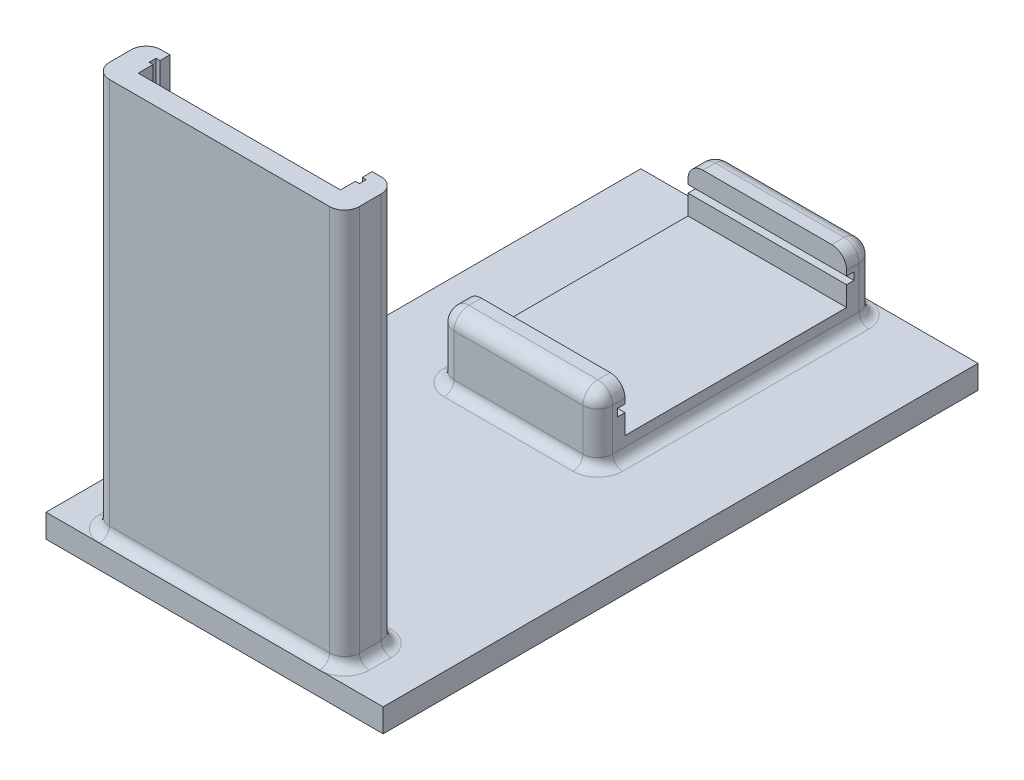
SolidWorks part; units mm, degrees
material "Melamine resin"
ref_plane "Front Plane" through (0, 0, 0) normal (0, 0, 1) x (1, 0, 0)
ref_plane "Top Plane" through (0, 0, 0) normal (0, 1, 0) x (1, 0, 0)
ref_plane "Right Plane" through (0, 0, 0) normal (1, 0, 0) x (0, 0, -1)
sketch "Sketch2" plane through (0, 0, 0) normal (0, 1, 0) x (1, 0, 0)
  line L1 (0, 0) -> (88.9, 0)
  line L2 (0, 0) -> (0, 152.4)
  line L3 (0, 152.4) -> (88.9, 152.4)
  line L10 (88.9, 152.4) -> (88.9, 0)
  dimension "D1" = 152.4
  dimension "D2" = 88.9
extrude "Boss-Extrude1" add sketch "Sketch2" along normal blind 5.9944 contours L3 L10 L1 L2
sketch "Sketch4" plane through (0, 5.9944, 0) normal (0, 1, 0) x (1, 0, 0)
  line L0 (0, 0) -> (0, 152.4) construction
  line L1 (0, 0) -> (88.9, 0) construction
  circle A0 centre (45.72, 109.8713) radius 2.7305
  circle A1 centre (45.72, 33.6713) radius 2.7305
  dimension "D3" = 5.461
  dimension "D4" = 5.461
  dimension "D1" = 76.2
  dimension "D2" = 45.72
  dimension "D5" = 33.6713
extrude "Cut-Extrude2" cut sketch "Sketch4" against normal through all both
sketch "Sketch5" plane through (0, 5.9944, 0) normal (0, 1, 0) x (1, 0, 0)
  line L0 (0, 152.4) -> (88.9, 152.4) construction
  line L1 (12.446, 15.748) -> (76.454, 15.748)
  line L2 (12.446, 15.748) -> (12.446, 2.54)
  line L3 (12.446, 2.54) -> (76.454, 2.54)
  line L4 (76.454, 15.748) -> (76.454, 2.54)
  line L5 (18.542, 7.62) -> (70.358, 7.62)
  line L6 (18.542, 7.62) -> (18.542, 15.748)
  line L7 (18.542, 15.748) -> (70.358, 15.748)
  line L8 (70.358, 7.62) -> (70.358, 15.748)
  line L9 (17.526, 13.208) -> (71.374, 13.208)
  line L10 (17.526, 13.208) -> (17.526, 11.43)
  line L11 (17.526, 11.43) -> (71.374, 11.43)
  line L12 (71.374, 13.208) -> (71.374, 11.43)
  line L13 (0, 0) -> (88.9, 0) construction
  point P16 (44.45, 152.4)
  point P17 (44.45, 15.748)
  dimension "D1" = 53.848
  dimension "D2" = 1.016
  dimension "D3" = 1.016
  dimension "D4" = 3.81
  dimension "D5" = 2.54
  dimension "D6" = 5.08
  dimension "D7" = 5.08
  dimension "D8" = 1.778
  dimension "D9" = 2.54
  dimension "D10" = 5.08
extrude "Boss-Extrude2" add sketch "Sketch5" along normal blind 101.6 contours L9 L12 L11 L8 L5 L6 L10 L1 L2 L3 L4 region at (44.45, 5.9944, -6.5736)
fillet "Fillet1" radius 3.81 4 edges at (12.446, 56.7944, -2.54) (12.446, 56.7944, -15.748) (76.454, 56.7944, -2.54) (76.454, 56.7944, -15.748)
fillet "Fillet2" radius 2.54 9 edges at (17.399, 5.9944, -15.748) (13.5619, 5.9944, -14.6321) (12.446, 5.9944, -9.144) (13.5619, 5.9944, -3.6559) (71.501, 5.9944, -15.748) (75.3381, 5.9944, -14.6321) (76.454, 5.9944, -9.144) (75.3381, 5.9944, -3.6559) (44.45, 5.9944, -2.54)
ref_plane "Plane1" through (44.45, 0, 0) normal (-1, 0, 0) x (0, 0, 1)
sketch "Sketch6" plane through (44.45, 0, 0) normal (-1, 0, 0) x (0, 0, 1)
  line L0 (0, 5.9944) -> (-152.4, 5.9944) construction
  line L1 (0, 5.9944) -> (-152.4, 5.9944)
  line L3 (-149.86, 5.9944) -> (-79.121, 5.9944)
  line L4 (-149.86, 5.9944) -> (-149.86, 23.1394)
  line L5 (-149.86, 23.1394) -> (-79.121, 23.1394)
  line L6 (-79.121, 5.9944) -> (-79.121, 23.1394)
  line L7 (-142.875, 23.1394) -> (-86.106, 23.1394)
  line L8 (-142.875, 23.1394) -> (-142.875, 11.0744)
  line L9 (-142.875, 11.0744) -> (-86.106, 11.0744)
  line L10 (-86.106, 23.1394) -> (-86.106, 11.0744)
  line L11 (-144.78, 18.0594) -> (-84.201, 18.0594)
  line L12 (-144.78, 18.0594) -> (-144.78, 16.1544)
  line L13 (-144.78, 16.1544) -> (-84.201, 16.1544)
  line L14 (-84.201, 18.0594) -> (-84.201, 16.1544)
  line L15 (-152.4, 5.9944) -> (-152.4, 0) construction
  dimension "D1" = 60.579
  dimension "D2" = 1.905
  dimension "D3" = 1.905
  dimension "D4" = 1.905
  dimension "D5" = 5.08
  dimension "D6" = 5.08
  dimension "D7" = 5.08
  dimension "D8" = 5.08
  dimension "D9" = 5.08
  dimension "D10" = 2.54
extrude "Boss-Extrude3" add sketch "Sketch6" along normal mid plane 40.64 contours L11 L14 L13 L10 L9 L8 L12 L5 L4 L1 L6 region at (44.45, 6.7223, -114.4905)
fillet "Fillet3" radius 3.81 2 edges at (44.45, 23.1394, -79.121) (44.45, 23.1394, -149.86)
fillet "Fillet6" radius 3.81 12 edges at (24.13, 23.1394, -84.5185) (24.13, 22.0235, -80.2369) (64.77, 23.1394, -84.5185) (64.77, 22.0235, -80.2369) (64.77, 23.1394, -144.4625) (64.77, 22.0235, -148.7441) (24.13, 23.1394, -144.4625) (24.13, 22.0235, -148.7441) (24.13, 12.6619, -79.121) (64.77, 12.6619, -79.121) (64.77, 12.6619, -149.86) (24.13, 12.6619, -149.86)
fillet "Fillet7" radius 2.54 8 edges at (25.2459, 5.9944, -80.2369) (44.45, 5.9944, -79.121) (63.6541, 5.9944, -80.2369) (64.77, 5.9944, -114.4905) (63.6541, 5.9944, -148.7441) (44.45, 5.9944, -149.86) (25.2459, 5.9944, -148.7441) (24.13, 5.9944, -114.4905)
sketch "Sketch7" plane through (0, 5.9944, 0) normal (0, 1, 0) x (1, 0, 0)
  line L0 (0, 0) -> (16.256, 0) construction
  line L1 (0, 152.4) -> (2.54, 152.4)
  line L2 (0, 152.4) -> (0, 0)
  line L3 (0, 0) -> (2.54, 0)
  line L4 (2.54, 152.4) -> (2.54, 0)
  dimension "D1" = 2.54
extrude "Cut-Extrude3" cut sketch "Sketch7" against normal through all both
equation "\"threaded_insert_hole\"=0.1472"
equation "\"th\"=1.25249"
